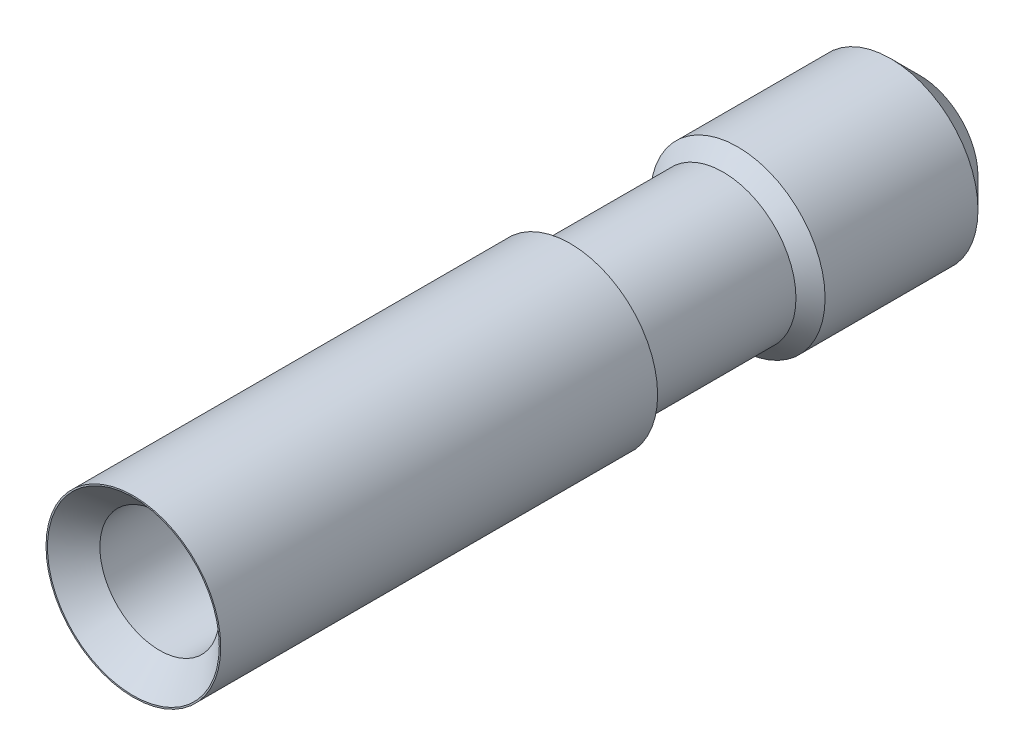
SolidWorks part; units mm, degrees
material "1.4000 (X6Cr13)"
ref_plane "Plan de face" through (0, 0, 0) normal (0, 0, 1) x (1, 0, 0)
ref_plane "Plan de dessus" through (0, 0, 0) normal (0, 1, 0) x (1, 0, 0)
ref_plane "Plan de droite" through (0, 0, 0) normal (1, 0, 0) x (0, 0, -1)
sketch "Esquisse1" plane through (0, 0, 0) normal (0, 0, 1) x (1, 0, 0)
  circle A0 centre (0, 0) radius 3
  dimension "D1" = 6
extrude "Boss.-Extru.1" add sketch "Esquisse1" along normal blind 27 contours A0
cosmetic thread "Représentation de filetage1" parameters "D1"=5, "D2"=4.891
sketch "Esquisse7" plane through (0, 0, 27) normal (0, 0, 1) x (1, 0, 0)
  circle A1 centre (0, 0) radius 2.05
  dimension "D1" = 4.1
hole_wizard "Diamètre du perçage Ø2.0 (2)1" positions "Esquisse5" profile "Esquisse4" hole size "Ø2.0" standard "ISO"
sketch "Esquisse5" plane through (0, 0, 0) normal (0, 0, -1) x (-1, 0, 0)
  point P0 (0, 0)
sketch "Esquisse4" plane through (0, 0, 0) normal (1, 0, 0) x (0, 1, 0)
  line L0 (0, 0) -> (0, 3)
  line L1 (0, 3) -> (1, 3)
  line L2 (1, 3) -> (1, 0)
  line L5 (1, 0) -> (0, 0)
  line L10 (0, 3) -> (-1, 3) construction
  line L11 (0, -6.35) -> (0, 107.95) construction
  dimension "Diamètre du perçage" = 2
  dimension "Profondeur du perçage" = 3
  dimension "Angle de pointe" = 180
sketch "Esquisse6" plane through (0, 0, 27) normal (0, 0, 1) x (1, 0, 0)
  line L1 (-6.0949, -5.2635) -> (5.6553, -5.2635)
  line L2 (-6.0949, -5.2635) -> (-6.0949, 6.1211)
  line L3 (-6.0949, 6.1211) -> (5.6553, 6.1211)
  line L4 (5.6553, -5.2635) -> (5.6553, 6.1211)
  circle A0 centre (0, 0) radius 2.5
  dimension "D1" = 5
extrude "Enlèv. mat.-Extru.1" cut sketch "Esquisse6" against normal blind 6 from offset 15 offset against normal yes
chamfer "Chanfrein1" distance 1 angle 45 1 edges at (3, 0, 0)
chamfer "Chanfrein2" distance 0.75 angle 45 1 edges at (2.5, 0, 6)
hole_wizard "Diamètre du perçage Ø4.1 (4.1)1" positions "Esquisse9" profile "Esquisse8" hole size "Ø4.1" standard "ISO"
sketch "Esquisse9" plane through (0, 0, 27) normal (0, 0, 1) x (1, 0, 0)
  point P0 (0, 0)
sketch "Esquisse8" plane through (0, 0, 27) normal (1, 0, 0) x (0, -1, 0)
  line L0 (0, 0) -> (0, 24)
  line L1 (0, 24) -> (2.05, 24)
  line L2 (2.05, 24) -> (2.05, 0)
  line L5 (2.05, 0) -> (0, 0)
  line L10 (0, 24) -> (-2.05, 24) construction
  line L11 (0, -6.35) -> (0, 107.95) construction
  dimension "Diamètre du perçage" = 4.1
  dimension "Profondeur du perçage" = 24
  dimension "Angle de pointe" = 180
chamfer "Chanfrein3" distance 0.9 angle 45 1 edges at (2.05, 0, 27)
